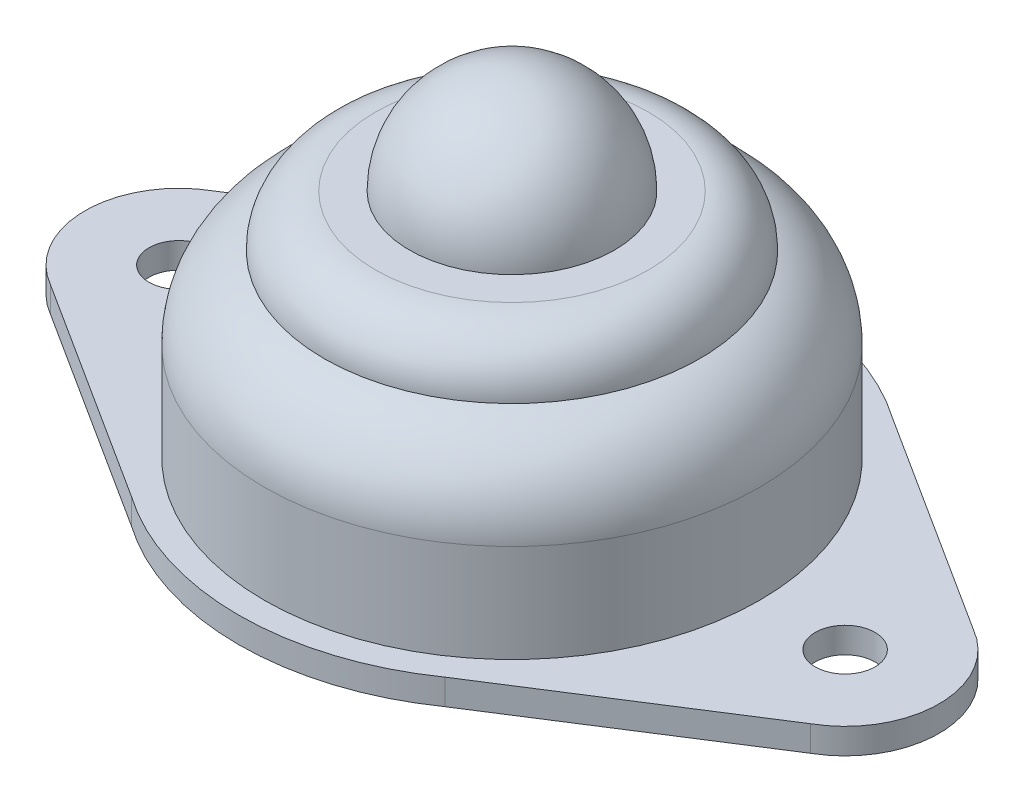
SolidWorks part; units mm, degrees
material "1023 Carbon Steel Sheet (SS)"
ref_plane "Front Plane" through (0, 0, 0) normal (0, 0, 1) x (1, 0, 0)
ref_plane "Top Plane" through (0, 0, 0) normal (0, 1, 0) x (1, 0, 0)
ref_plane "Right Plane" through (0, 0, 0) normal (1, 0, 0) x (0, 0, -1)
sketch "Sketch1" plane through (0, 0, 0) normal (0, 1, 0) x (1, 0, 0)
  line L0 (-19.5, 0) -> (19.5, 0) construction
  line L1 (-19.5, 0) -> (-22.25, 4.7631) construction
  line L2 (0, 0) -> (-9.1772, -13.1064) construction
  line L3 (0, 0) -> (-9.1772, 13.1064) construction
  line L4 (-9.1772, -13.1064) -> (-9.1772, 13.1064) construction
  line L5 (-19.5, 0) -> (-22.25, -4.7631) construction
  line L6 (-22.25, -4.7631) -> (-22.25, 4.7631) construction
  line L7 (-22.25, -4.7631) -> (-9.1772, -13.1064)
  line L8 (-22.25, 4.7631) -> (-9.1772, 13.1064)
  line L9 (0, -16) -> (0, 16) construction
  line L10 (22.25, 4.7631) -> (9.1772, 13.1064)
  line L11 (22.25, -4.7631) -> (9.1772, -13.1064)
  circle A0 centre (-19.5, 0) radius 1.75
  circle A1 centre (19.5, 0) radius 1.75
  arc A2 (-22.25, 4.7631) -> (-22.25, -4.7631) centre (-19.5, 0) ccw
  arc A3 (22.25, -4.7631) -> (22.25, 4.7631) centre (19.5, 0) ccw
  arc A4 (-9.1772, -13.1064) -> (9.1772, -13.1064) centre (0, 0) ccw
  arc A5 (9.1772, 13.1064) -> (-9.1772, 13.1064) centre (0, 0) ccw
  point P4 (0, 0)
  dimension "D1" = 3.5
  dimension "D3" = 11
  dimension "D4" = 32
  dimension "D2" = 39
  dimension "D5" = 30
  dimension "D6" = 35
extrude "Boss-Extrude1" add sketch "Sketch1" along normal blind 1.5
sketch "Sketch2" plane through (0, 1.5, 0) normal (0, 1, 0) x (1, 0, 0)
  circle A0 centre (0, 0) radius 14.5
  dimension "D1" = 29
extrude "Boss-Extrude2" add sketch "Sketch2" along normal blind 10.5
sketch "Sketch3" plane through (0, 12, 0) normal (0, 1, 0) x (1, 0, 0)
  circle A0 centre (0, 0) radius 11
  dimension "D1" = 22
extrude "Boss-Extrude3" add sketch "Sketch3" along normal blind 3
sketch "Sketch5" plane through (0, 0, 0) normal (0, 0, 1) x (1, 0, 0)
  line L0 (0, 15) -> (0, 21)
  line L1 (11, 15) -> (-11, 15) construction
  line L2 (6, 15) -> (0, 15)
  arc A0 (0, 21) -> (6, 15) centre (0, 15) cw
  dimension "D1" = 6
revolve "Revolve1" add sketch "Sketch5" angle 360 about L0
fillet "Fillet1" radius 5 1 edges at (0, 12, 14.5)
fillet "Fillet2" radius 3 1 edges at (0, 15, 11)
